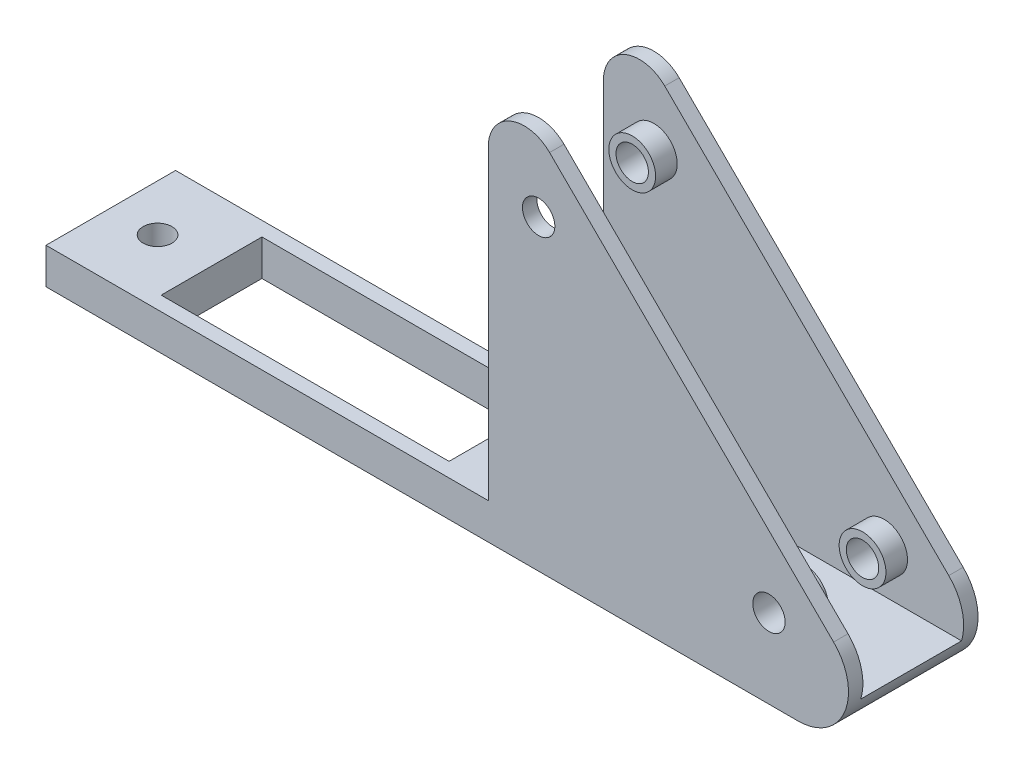
SolidWorks part; units mm, degrees
ref_plane "Front Plane" through (0, 0, 0) normal (0, 0, 1) x (1, 0, 0)
ref_plane "Top Plane" through (0, 0, 0) normal (0, 1, 0) x (1, 0, 0)
ref_plane "Right Plane" through (0, 0, 0) normal (1, 0, 0) x (0, 0, -1)
sketch "Sketch1" plane through (0, 0, 0) normal (0, 1, 0) x (1, 0, 0)
  line L1 (-36, -9) -> (80.4457, -9)
  line L2 (-36, -9) -> (-36, 9)
  line L3 (-36, 9) -> (80.4457, 9)
  line L4 (80.4457, -9) -> (80.4457, 9)
  line L7 (-22, 7) -> (18, 7)
  line L8 (-22, 7) -> (-22, -7)
  line L9 (-22, -7) -> (18, -7)
  line L10 (18, 7) -> (18, -7)
  circle A0 centre (-29.5, 0) radius 2
  circle A1 centre (25.5, 0) radius 2
  point P0 (0, 0)
  dimension "D5" = 4
  dimension "D6" = 4
  dimension "D1" = 18
  dimension "D2" = 2
  dimension "D3" = 2
  dimension "D4" = 14
  dimension "D7" = 40
  dimension "D8" = 7.5
  dimension "D9" = 7.5
extrude "Boss-Extrude1" add sketch "Sketch1" along normal blind 5
sketch "Sketch2" plane through (0, 0, 9) normal (0, 0, 1) x (1, 0, 0)
  line L0 (25.4457, 5) -> (25.4457, 59.6015)
  line L1 (-36, 5) -> (80.4457, 5) construction
  line L2 (25.4457, 5) -> (25.4457, 0)
  line L3 (25.4457, 59.6015) -> (80.4457, 5)
  line L4 (80.4457, 5) -> (25.4457, 5)
  line L5 (-36, 0) -> (80.4457, 0) construction
  line L6 (25.4457, 0) -> (80.4457, 0)
  line L7 (80.4457, 0) -> (80.4457, 5)
  line L8 (80.4457, 5) -> (85.4822, 0)
  line L9 (85.4822, 0) -> (77.448, 0)
  circle A0 centre (32.4471, 42.64) radius 2.25
  circle A1 centre (64.4457, 11) radius 2.25
  point P16 (83.4527, 0)
  point P17 (83.9309, 0)
  point P18 (25.4457, 59.6015)
  line M3 (80.4457, 0) -> (80.4457, 5)
  line M4 (80.4457, 5) -> (-36, 5)
  dimension "D7" = 4.5
  dimension "D8" = 4.5
  dimension "D1" = 45
  dimension "D2" = 31.64
  dimension "D3" = 31.9986
  dimension "D4" = 55
  dimension "D5" = 16
  dimension "D6" = 6
extrude "Boss-Extrude2" add sketch "Sketch2" against normal blind 2 contours L9 L8 M3 | L3 L0 A1 A0 M4 region at (43.678, 23.1222, 9) region at (82.1245, 1.6667, 9)
sketch "Sketch4" plane through (0, 0, -9) normal (0, 0, -1) x (-1, 0, 0)
  line L0 (-80.4457, 5) -> (-25.4457, 59.6015)
  line L1 (-25.4457, 59.6015) -> (-25.4457, 5)
  line L2 (-80.4457, 5) -> (36, 5) construction
  line L3 (-25.4457, 5) -> (-25.4457, 0)
  line L4 (-80.4457, 0) -> (36, 0) construction
  line L5 (-25.4457, 0) -> (-80.4457, 0)
  line L6 (-80.4457, 0) -> (-80.4457, 5)
  line L7 (-80.4457, 5) -> (-85.4822, 0)
  line L8 (-85.4822, 0) -> (-80.4457, 0)
  line L9 (-80.4457, 0) -> (-80.4048, -0.0186)
  circle A0 centre (-32.4471, 42.64) radius 2.25
  circle A1 centre (-64.4457, 11) radius 2.25
  line M3 (36, 5) -> (-80.4457, 5)
  line M4 (-80.4457, 5) -> (-80.4457, 0)
  dimension "D1" = 4.5
  dimension "D2" = 4.5
extrude "Boss-Extrude3" add sketch "Sketch4" against normal blind 2 contours L1 L0 A1 A0 M3 | L7 L8 M4 region at (82.1245, 1.6667, -9) region at (43.678, 23.1222, -9)
fillet "Fillet2" radius 7 1 edges at (85.4822, 0, -8)
fillet "Fillet3" radius 5 2 edges at (25.4457, 59.6015, -8) (25.4457, 59.6015, 8)
sketch "Sketch6" plane through (0, 0, 7) normal (0, 0, -1) x (-1, 0, 0)
  circle A2 centre (-64.4457, 11) radius 2.25
  circle A3 centre (-64.4457, 11) radius 3.25
  dimension "D2" = 6.5
extrude "Boss-Extrude4" add sketch "Sketch6" along normal blind 3
sketch "Sketch7" plane through (0, 0, -7) normal (0, 0, 1) x (1, 0, 0)
  circle A0 centre (32.4471, 42.64) radius 2.25
  circle A1 centre (32.4471, 42.64) radius 3.25
  circle A2 centre (64.4457, 11) radius 2.25
  circle A3 centre (64.4457, 11) radius 3.25
  dimension "D1" = 6.5
  dimension "D2" = 6.5
extrude "Boss-Extrude5" add sketch "Sketch7" along normal blind 3
